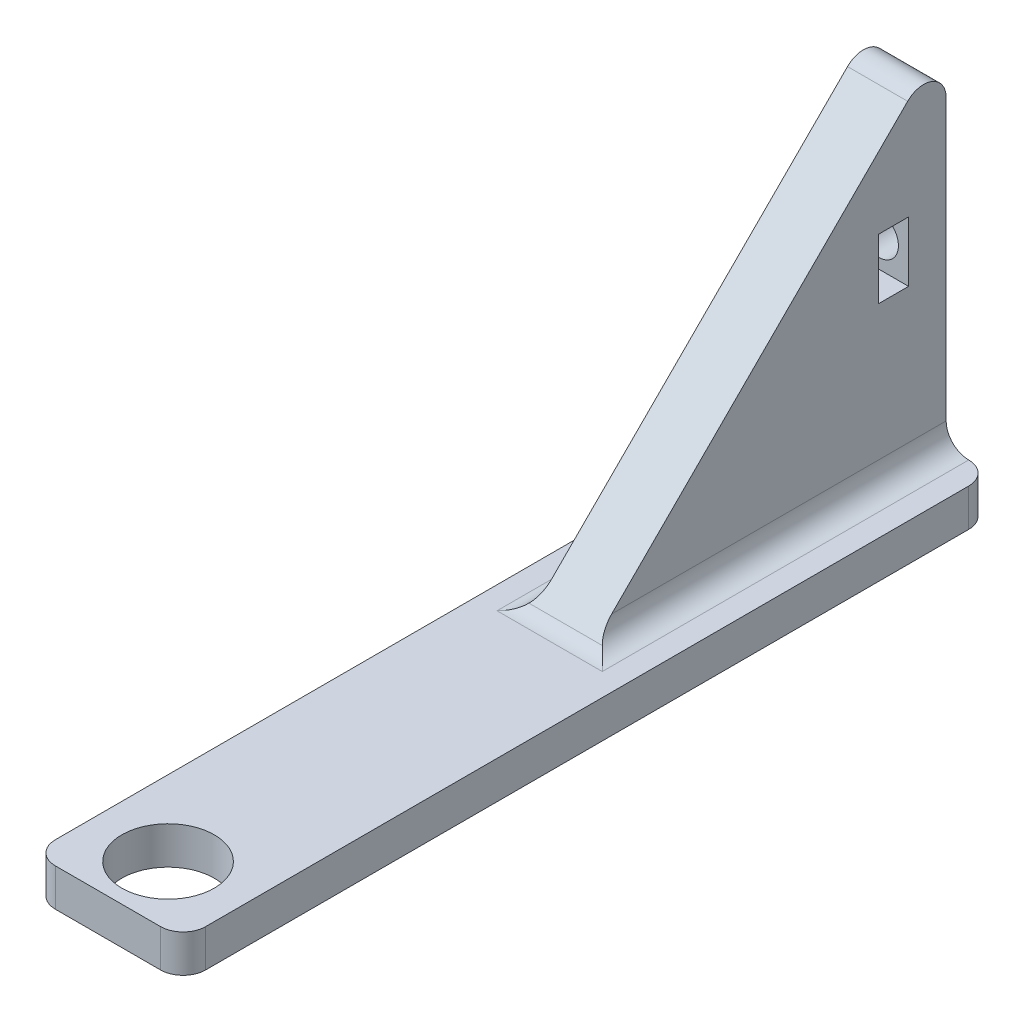
SolidWorks part; units mm, degrees
ref_plane "Front Plane" through (0, 0, 0) normal (0, 0, 1) x (1, 0, 0)
ref_plane "Top Plane" through (0, 0, 0) normal (0, 1, 0) x (1, 0, 0)
ref_plane "Right Plane" through (0, 0, 0) normal (1, 0, 0) x (0, 0, -1)
sketch "Sketch3" plane through (0, 0, 0) normal (0, 1, 0) x (1, 0, 0)
  line L1 (0, 0) -> (20, 0)
  line L2 (0, 0) -> (0, -107.5)
  line L3 (0, -107.5) -> (20, -107.5)
  line L4 (20, 0) -> (20, -107.5)
  circle A0 centre (10, -99.5) radius 6.15
  dimension "D4" = 12.3
  dimension "D1" = 107.5
  dimension "D2" = 20
  dimension "D3" = 10
  dimension "D5" = 8
extrude "Boss-Extrude2" add sketch "Sketch3" along normal blind 5
ref_plane "Plane1" through (10, 0, 0) normal (1, 0, 0) x (0, 0, -1)
sketch "Sketch4" plane through (10, 0, 0) normal (1, 0, 0) x (0, 0, -1)
  line L0 (0, 5) -> (0, 52.5)
  line L1 (0, 5) -> (0, 0) construction
  line L2 (0, 52.5) -> (-47.5, 5)
  line L3 (-107.5, 5) -> (0, 5) construction
  line L4 (-47.5, 5) -> (0, 5)
  dimension "D1" = 47.5
  dimension "D2" = 47.5
extrude "Boss-Extrude3" add sketch "Sketch4" along normal blind 4 and the other way blind 4
sketch "Sketch5" plane through (0, 0, 0) normal (0, 0, -1) x (-1, 0, 0)
  line L5 (-20, 0) -> (0, 0) construction
  line L6 (-10, 28.875) -> (-10, -28.875) construction
  circle A1 centre (-10, 30) radius 2.65
  dimension "D2" = 30
  dimension "D3" = 5.3
extrude "Cut-Extrude1" cut sketch "Sketch5" against normal blind 12
sketch "Sketch6" plane through (14, 0, 0) normal (1, 0, 0) x (0, 0, -1)
  line L0 (-107.5, 0) -> (0, 0) construction
  line L1 (-9, 26) -> (-5, 26)
  line L2 (-9, 26) -> (-9, 34)
  line L3 (-9, 34) -> (-5, 34)
  line L4 (-5, 26) -> (-5, 34)
  line L5 (0, 5) -> (0, 52.5) construction
  dimension "D1" = 8
  dimension "D2" = 4
  dimension "D3" = 26
  dimension "D4" = 5
extrude "Cut-Extrude2" cut sketch "Sketch6" against normal through all
fillet "Fillet1" radius 3 8 edges at (20, 2.5, 107.5) (0, 2.5, 107.5) (6, 5, 23.75) (10, 5, 47.5) (14, 5, 23.75) (10, 52.5, 0) (20, 2.5, 0) (0, 2.5, 0)
equation "\"D3@Sketch3\"=\"D2@Sketch3\"/2"
equation "\"D2@Sketch4\"=\"D1@Sketch4\""
